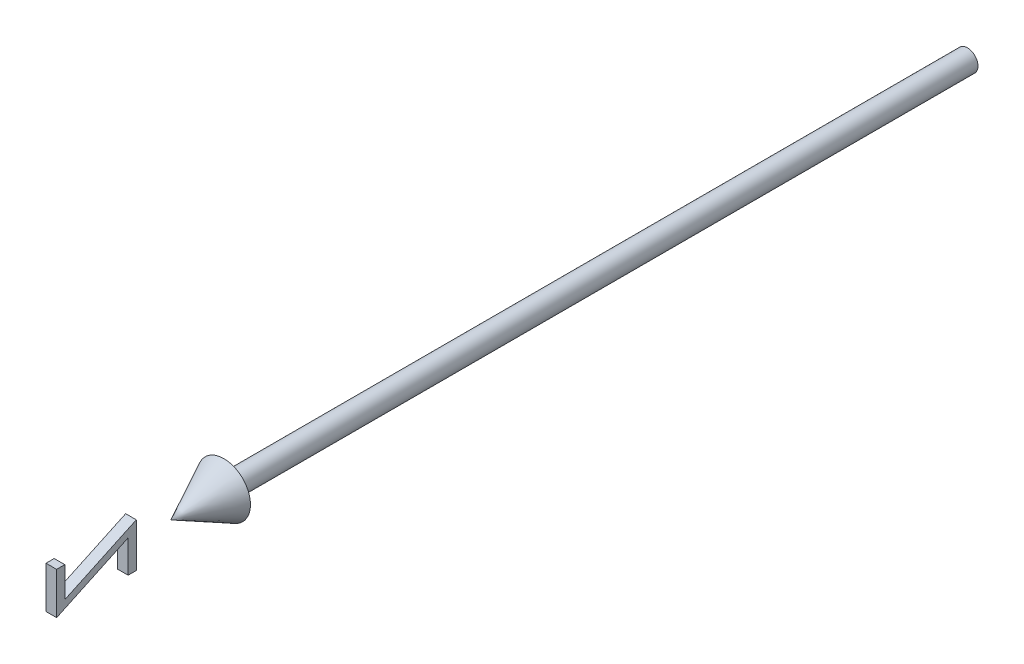
SolidWorks part; units mm, degrees
ref_plane "Front Plane" through (0, 0, 0) normal (0, 0, 1) x (1, 0, 0)
ref_plane "Top Plane" through (0, 0, 0) normal (0, 1, 0) x (1, 0, 0)
ref_plane "Right Plane" through (0, 0, 0) normal (1, 0, 0) x (0, 0, -1)
sketch "Sketch2" plane through (0, 0, 0) normal (0, 1, 0) x (1, 0, 0)
  line L0 (0, 41.95) -> (0, -114.4521) construction
  line L1 (-36.8894, 0) -> (41.4965, 0) construction
  line L2 (0, -150) -> (5, -140)
  line L3 (5, -140) -> (2, -140)
  line L4 (2, -140) -> (2, 0)
  line L5 (2, 0) -> (0, 0)
  line L6 (0, 0) -> (0, -150)
  dimension "D1" = 150
  dimension "D2" = 2
  dimension "D3" = 10
  dimension "D4" = 5
revolve "Revolve1" add sketch "Sketch2" angle 360 about L0
sketch "Sketch3" plane through (0, 0, 0) normal (1, 0, 0) x (0, -1, 0)
  line L0 (0, -101.5706) -> (0, -127.8138) construction
  line L1 (-4.8486, -157.5) -> (14.1256, -157.5) construction
  line L2 (-19.7795, 0) -> (19.7795, 0) construction
  text T0 "Z" font "Century Gothic" height 15
  dimension "D1" = 157.5
extrude "Boss-Extrude1" add sketch "Sketch3" against normal blind 1 and the other way blind 1 separate body
equation "\"D1@Sketch2\"=\"frame_arrow_length\""
equation "\"D2@Sketch2\"=\"frame_arrow_odA\"/2"
equation "\"D4@Sketch2\"=\"frame_arrow_head_od\""
equation "\"D3@Sketch2\"=\"frame_arrow_head_length\""
equation "\"frame_arrow_length\"=150"
equation "\"frame_arrow_head_length\"=10"
equation "\"frame_arrow_head_od\"=5"
equation "\"frame_arrow_odA\"=4"
equation "\"D1@Sketch3\"=\"frame_arrow_length\"*1.05"
